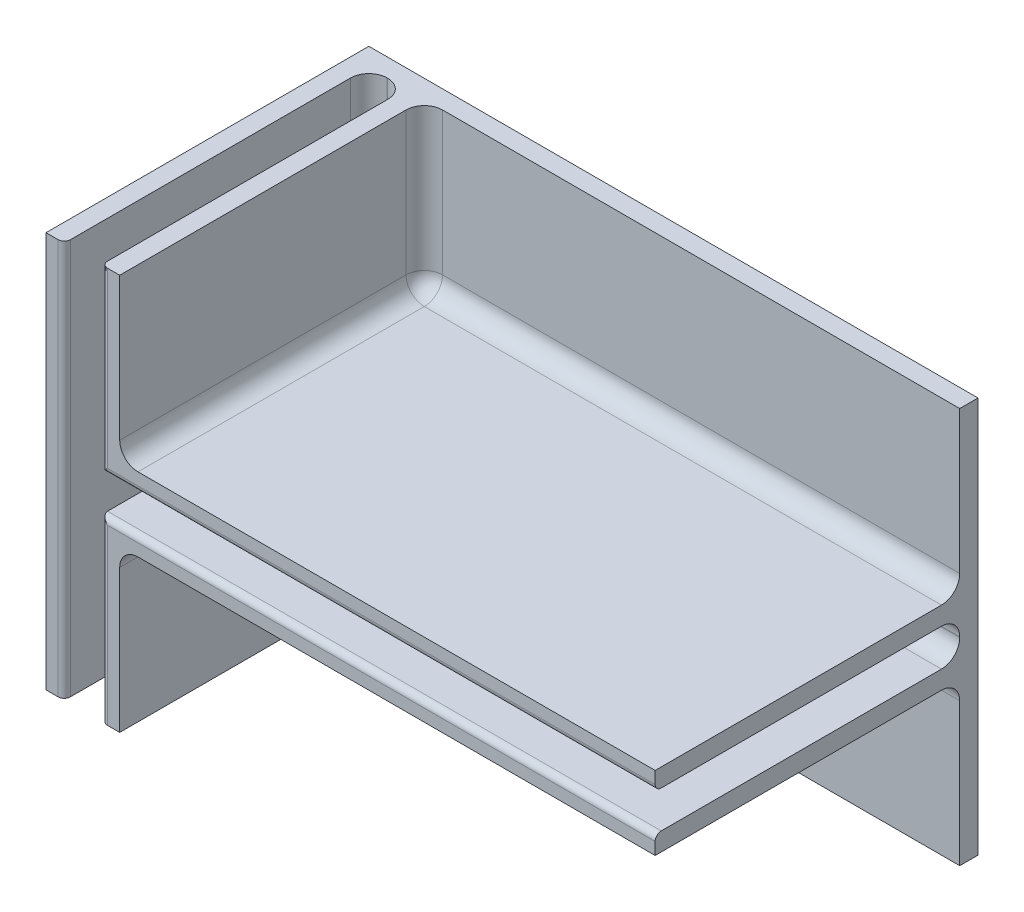
SolidWorks part; units mm, degrees
ref_plane "Front" through (0, 0, 0) normal (0, 0, 1) x (1, 0, 0)
ref_plane "Top" through (0, 0, 0) normal (0, 1, 0) x (1, 0, 0)
ref_plane "Right" through (0, 0, 0) normal (1, 0, 0) x (0, 0, -1)
sketch "Sketch1" plane through (0, 0, 0) normal (0, 0, 1) x (1, 0, 0)
  line L5 (0, 0) -> (100, 0)
  line L6 (0, 0) -> (0, 65)
  line L7 (0, 65) -> (100, 65)
  line L8 (100, 0) -> (100, 65)
  dimension "D1" = 65
  dimension "D2" = 100
extrude "Boss-Extrude1" add sketch "Sketch1" along normal blind 3
sketch "Sketch2" plane through (0, 0, 3) normal (0, 0, 1) x (1, 0, 0)
  line L0 (9.1, 65) -> (9.1, 35.55)
  line L25 (0, 65) -> (3, 65)
  line L26 (0, 65) -> (0, 0)
  line L27 (0, 0) -> (3, 0)
  line L28 (3, 65) -> (3, 0)
  line L29 (0, 0) -> (100, 0) construction
  line L48 (100, 65) -> (0, 65) construction
  line L50 (9.1, 35.55) -> (100, 35.55)
  line L51 (100, 0) -> (100, 65) construction
  line L52 (9.1, 0) -> (9.1, 29.45)
  line L53 (9.1, 29.45) -> (100, 29.45)
  line L54 (9.1, 65) -> (12.1, 65)
  line L55 (12.1, 65) -> (12.1, 38.55)
  line L56 (12.1, 38.55) -> (100, 38.55)
  line L57 (100, 38.55) -> (100, 35.55)
  line L58 (12.1, 0) -> (12.1, 26.45)
  line L59 (12.1, 26.45) -> (100, 26.45)
  line L60 (9.1, 0) -> (12.1, 0)
  line L61 (100, 26.45) -> (100, 29.45)
  dimension "D1" = 6.1
  dimension "D2" = 3
  dimension "D3" = 6.1
extrude "Boss-Extrude2" add sketch "Sketch2" along normal blind 50
fillet "Fillet2" radius 3 11 edges at (12.1, 26.45, 28) (56.05, 26.45, 3) (12.1, 13.225, 3) (12.1, 38.55, 28) (56.05, 38.55, 3) (12.1, 51.775, 3) (54.55, 29.45, 3) (54.55, 35.55, 3) (9.1, 50.275, 3) (9.1, 14.725, 3) (3, 32.5, 3)
fillet "Fillet3" radius 1 5 edges at (54.55, 29.45, 53) (54.55, 35.55, 53) (9.1, 50.275, 53) (9.1, 14.725, 53) (3, 32.5, 53)
